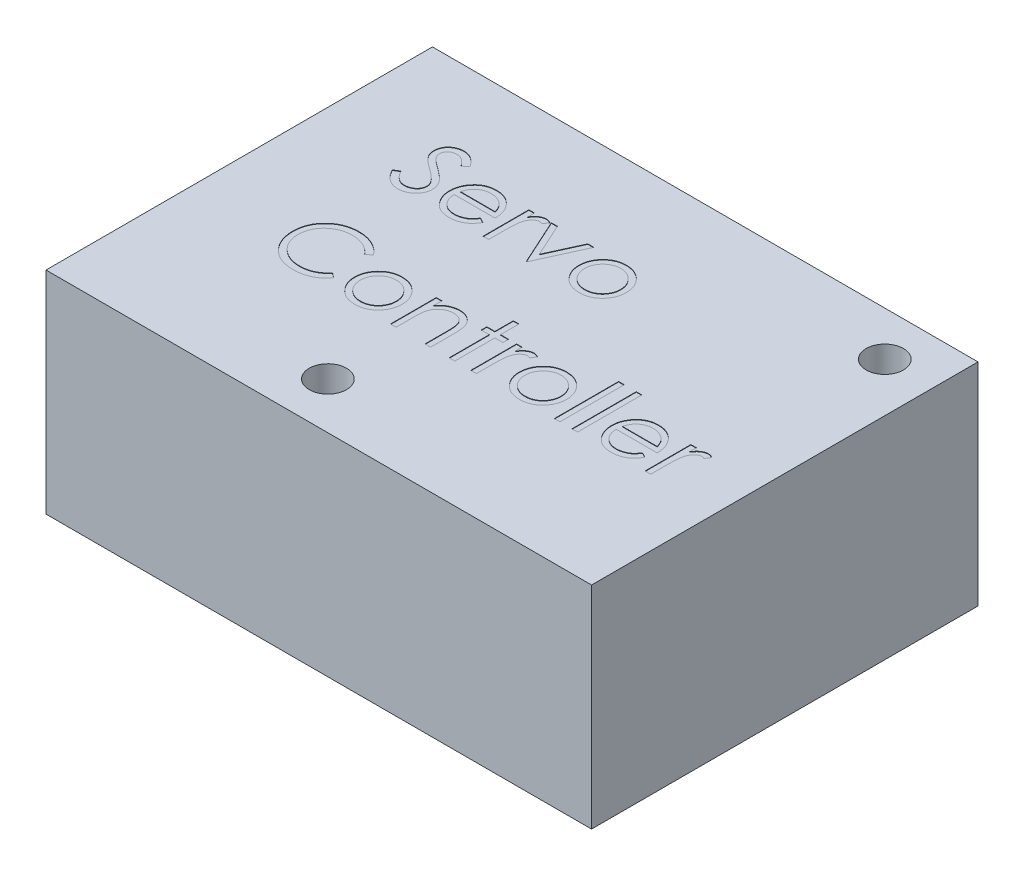
SolidWorks part; units mm, degrees
ref_plane "Front Plane" through (0, 0, 0) normal (0, 0, 1) x (1, 0, 0)
ref_plane "Top Plane" through (0, 0, 0) normal (0, 1, 0) x (1, 0, 0)
ref_plane "Right Plane" through (0, 0, 0) normal (1, 0, 0) x (0, 0, -1)
sketch "Sketch1" plane through (0, 0, 0) normal (0, 1, 0) x (1, 0, 0)
  line L1 (-15.24, -10.795) -> (15.24, -10.795)
  line L2 (-15.24, -10.795) -> (-15.24, 10.795)
  line L3 (-15.24, 10.795) -> (15.24, 10.795)
  line L4 (15.24, -10.795) -> (15.24, 10.795)
  line L5 (-15.24, -10.795) -> (15.24, 10.795) construction
  line L6 (-15.24, 10.795) -> (15.24, -10.795) construction
  point P0 (0, 0)
  dimension "D1" = 30.48
  dimension "D2" = 21.59
extrude "Boss-Extrude1" add sketch "Sketch1" along normal blind 11.811
hole_wizard "#45 (0.082) Diameter Hole1" positions "Sketch5" profile "Sketch4" hole size "#45" standard "ANSI Inch" end condition through all
sketch "Sketch5" plane through (0, 0, 0) normal (0, -1, 0) x (-1, 0, 0)
  line L0 (-15.24, -10.795) -> (-15.24, 10.795) construction
  line L1 (-15.24, 10.795) -> (15.24, 10.795) construction
  point P0 (2.0955, -8.1915)
  point P2 (-12.5095, 8.3185)
  dimension "D1" = 14.605
  dimension "D2" = 16.51
  dimension "D3" = 2.4765
  dimension "D4" = 2.7305
sketch "Sketch4" plane through (-2.0955, 0, 8.1915) normal (1, 0, 0) x (0, 0, -1)
  line L0 (0, 0) -> (0, 11.811)
  line L1 (0, 11.811) -> (1.0414, 11.811)
  line L2 (1.0414, 11.811) -> (1.0414, 0)
  line L5 (1.0414, 0) -> (0, 0)
  line L11 (0, -6.35) -> (0, 107.95) construction
  dimension "Thru Hole Dia." = 2.0828
  dimension "Thru Hole Depth" = 11.811
sketch "Sketch6" plane through (0, 11.811, 0) normal (0, 1, 0) x (1, 0, 0)
  text T0 "Servo\r\nController"
extrude "Cut-Extrude1" cut sketch "Sketch6" against normal blind 0.0254
